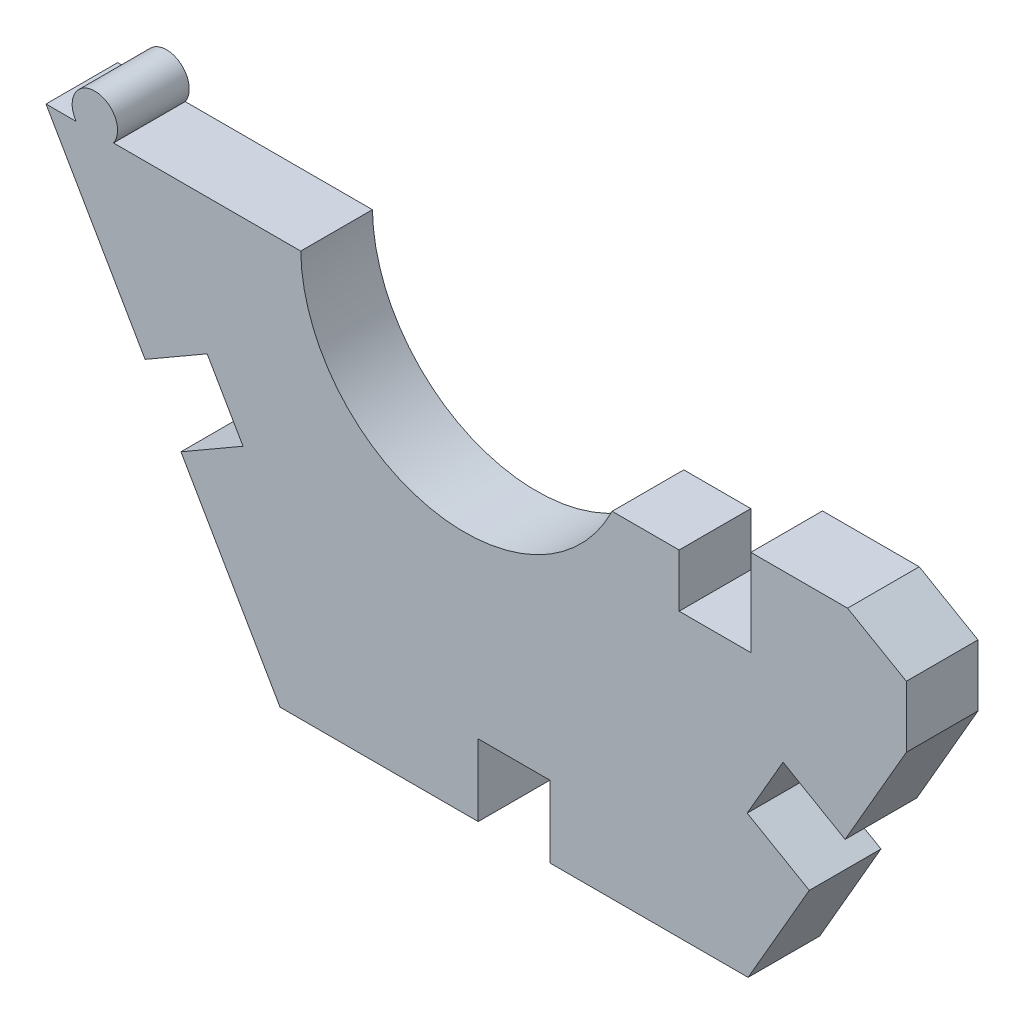
SolidWorks part; units mm, degrees
ref_plane "Front Plane" through (0, 0, 0) normal (0, 0, 1) x (1, 0, 0)
ref_plane "Top Plane" through (0, 0, 0) normal (0, 1, 0) x (1, 0, 0)
ref_plane "Right Plane" through (0, 0, 0) normal (1, 0, 0) x (0, 0, -1)
sketch "Sketch1" plane through (0, 0, 0) normal (0, 0, 1) x (1, 0, 0)
  line L0 (-1.524, -3.3705) -> (-1.524, -2.2428)
  line L1 (-1.524, -2.2428) -> (-2.9489, -2.2428)
  line L2 (-1.524, -3.3705) -> (0, -3.3705)
  line L3 (0, -3.3705) -> (0, -1.524)
  line L4 (-9.5684, -0.762) -> (-13.5482, -0.762)
  line L5 (-14.3419, -0.762) -> (-14.9835, -0.762)
  line L6 (-14.9835, -0.762) -> (-12.8769, -4.4107)
  line L8 (2.0566, -1.524) -> (0, -1.524)
  line L9 (2.0566, -1.524) -> (3.3055, -2.2451)
  line L10 (-14.1036, -0.762) -> (-9.5684, -8.6173) construction
  line L11 (-9.5684, -8.6173) -> (-0.4979, -8.6173) construction
  line L12 (-0.4979, -8.6173) -> (3.2122, -2.1912) construction
  line L13 (-10.0083, -9.3793) -> (-5.7951, -9.3793)
  line L14 (-0.0579, -9.3793) -> (1.2428, -7.1263)
  line L15 (-13.2238, -0.762) -> (-9.1285, -7.8553) construction
  line L16 (-9.1285, -7.8553) -> (-0.9378, -7.8553) construction
  line L17 (1.6238, -6.4664) -> (0.304, -5.7044) construction
  line L18 (-12.4959, -5.0706) -> (-11.1761, -4.3086) construction
  line L19 (-12.1149, -5.7306) -> (-10.7951, -4.9686)
  line L20 (-0.9378, -7.8553) -> (2.5523, -1.8102) construction
  line L21 (-5.7951, -7.8553) -> (-5.7951, -9.3793)
  line L22 (3.3055, -2.2451) -> (2.5523, -1.8102)
  line L23 (3.3055, -3.5535) -> (3.3055, -2.2451)
  line L24 (2.0048, -5.8065) -> (0.685, -5.0445)
  line L25 (-0.9378, -7.8553) -> (0.382, -8.6173) construction
  line L26 (-12.8769, -4.4107) -> (-11.5571, -3.6487)
  line L27 (-5.0331, -7.8553) -> (-5.0331, -9.3793) construction
  line L28 (-9.1285, -7.8553) -> (-10.4483, -8.6173) construction
  line L29 (-9.1285, -7.8553) -> (-9.1285, -9.3793) construction
  line L30 (-0.9378, -7.8553) -> (-0.9378, -9.3793) construction
  line L31 (-4.2711, -7.8553) -> (-4.2711, -9.3793)
  line L32 (1.2428, -7.1263) -> (-0.077, -6.3643)
  line L34 (-10.7951, -4.9686) -> (-11.5571, -3.6487)
  line L35 (-5.7951, -7.8553) -> (-4.2711, -7.8553)
  line L36 (-12.1149, -5.7306) -> (-10.0083, -9.3793)
  line L37 (-4.2711, -9.3793) -> (-0.0579, -9.3793)
  line L38 (0.685, -5.0445) -> (-0.077, -6.3643)
  line L39 (2.0048, -5.8065) -> (3.3055, -3.5535)
  arc A1 (-2.9489, -2.2428) -> (-9.5684, -0.762) centre (-6.0818, -0.7116) cw
  arc A2 (-13.5482, -0.762) -> (-14.3419, -0.762) centre (-13.9451, -0.4874) ccw
  point P17 (3.8721, -2.5722)
  point P20 (-13.4437, -0.381)
extrude "Boss-Extrude1" add sketch "Sketch1" along normal blind 1.524 contours L23 L39 L24 L38 L32 L14 L37 L31 L35 L21 L13 L36 L19 L34 L26 L6 L5 A2 L4 A1 L1 L0 L2 L3 L8 L9
